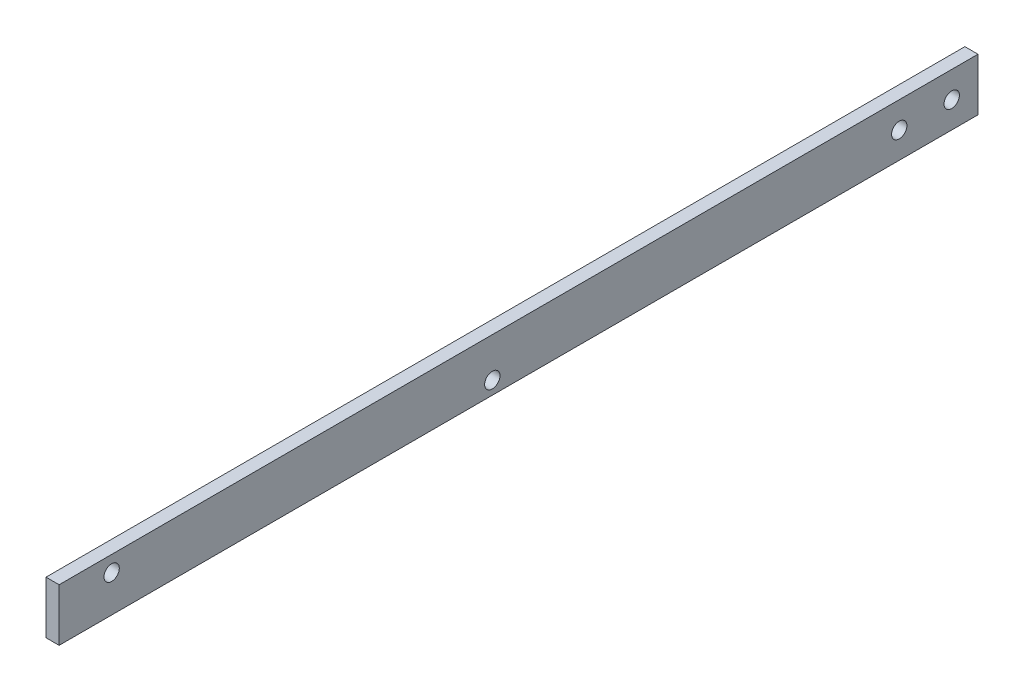
SolidWorks part; units mm, degrees
ref_plane "Front Plane" through (0, 0, 0) normal (0, 0, 1) x (1, 0, 0)
ref_plane "Top Plane" through (0, 0, 0) normal (0, 1, 0) x (1, 0, 0)
ref_plane "Right Plane" through (0, 0, 0) normal (1, 0, 0) x (0, 0, -1)
sketch "Sketch1" plane through (0, 0, 0) normal (0, 0, 1) x (1, 0, 0)
  line L1 (0, 0) -> (3.175, 0)
  line L2 (0, 0) -> (0, -12.7)
  line L3 (0, -12.7) -> (3.175, -12.7)
  line L4 (3.175, 0) -> (3.175, -12.7)
  dimension "D1" = 3.175
  dimension "D2" = 12.7
extrude "Boss-Extrude1" add sketch "Sketch1" along normal blind 222.25
sketch "Sketch2" plane through (3.175, 0, 0) normal (1, 0, 0) x (0, 0, -1)
  line L0 (0, -12.7) -> (0, 0) construction
  line L1 (-222.25, -12.7) -> (-222.25, 0) construction
  line L2 (-117.475, -6.35) -> (-117.475, 0)
  line L3 (-222.25, -12.7) -> (0, -12.7) construction
  line L5 (-222.25, 0) -> (0, 0) construction
  circle A0 centre (-117.475, -9.525) radius 3.175 construction
  point P6 (-209.55, -3.81)
  point P8 (-117.475, -9.525)
  point P10 (-6.35, -6.35)
  dimension "D3" = 6.35
  dimension "D4" = 104.775
  dimension "D5" = 6.35
  dimension "D1" = 12.7
  dimension "D2" = 3.81
  dimension "D6" = 6.35
  dimension "D7" = 6.35
hole_wizard "#6 (0.146) Diameter Hole1" positions "3DSketch1" profile "Sketch3" hole size "#6" standard "ANSI Inch" end condition through all
sketch3d "3DSketch1"
  point P2 (3.175, -3.81, 209.55)
sketch "Sketch3" plane through (3.175, -3.81, 209.55) normal (0, 1, 0) x (0, 0, -1)
  line L0 (0, 0) -> (0, 3.175)
  line L1 (0, 3.175) -> (1.8542, 3.175)
  line L2 (1.8542, 3.175) -> (1.8542, 0)
  line L5 (1.8542, 0) -> (0, 0)
  line L11 (0, -6.35) -> (0, 107.95) construction
  dimension "Thru Hole Dia." = 3.7084
  dimension "Thru Hole Depth" = 3.175
hole_wizard "#6 (0.146) Diameter Hole2" positions "3DSketch3" profile "Sketch5" hole size "#6" standard "ANSI Inch" end condition through all
sketch3d "3DSketch3"
  point P0 (3.175, -9.525, 117.475)
sketch "Sketch5" plane through (3.175, -9.525, 117.475) normal (0, 1, 0) x (0, 0, -1)
  line L0 (0, 0) -> (0, 3.175)
  line L1 (0, 3.175) -> (1.8542, 3.175)
  line L2 (1.8542, 3.175) -> (1.8542, 0)
  line L5 (1.8542, 0) -> (0, 0)
  line L11 (0, -6.35) -> (0, 107.95) construction
  dimension "Thru Hole Dia." = 3.7084
  dimension "Thru Hole Depth" = 3.175
sketch "Sketch9" plane through (3.175, 0, 0) normal (1, 0, 0) x (0, 0, -1)
  line L0 (0, -12.7) -> (0, 0) construction
  line L1 (-222.25, 0) -> (0, 0) construction
  point P0 (-6.35, -6.35)
  point P5 (-19.05, -6.35)
  dimension "D1" = 6.35
  dimension "D2" = 6.35
  dimension "D3" = 12.7
hole_wizard "#6 (0.146) Diameter Hole3" positions "3DSketch5" profile "Sketch10" hole size "#6" standard "ANSI Inch" end condition through all
sketch3d "3DSketch5"
  point P0 (3.175, -6.35, 6.35)
  point P4 (3.175, -6.35, 19.05)
sketch "Sketch10" plane through (3.175, -6.35, 6.35) normal (0, 1, 0) x (0, 0, -1)
  line L0 (0, 0) -> (0, 3.175)
  line L1 (0, 3.175) -> (1.8542, 3.175)
  line L2 (1.8542, 3.175) -> (1.8542, 0)
  line L5 (1.8542, 0) -> (0, 0)
  line L11 (0, -6.35) -> (0, 107.95) construction
  dimension "Thru Hole Dia." = 3.7084
  dimension "Thru Hole Depth" = 3.175
